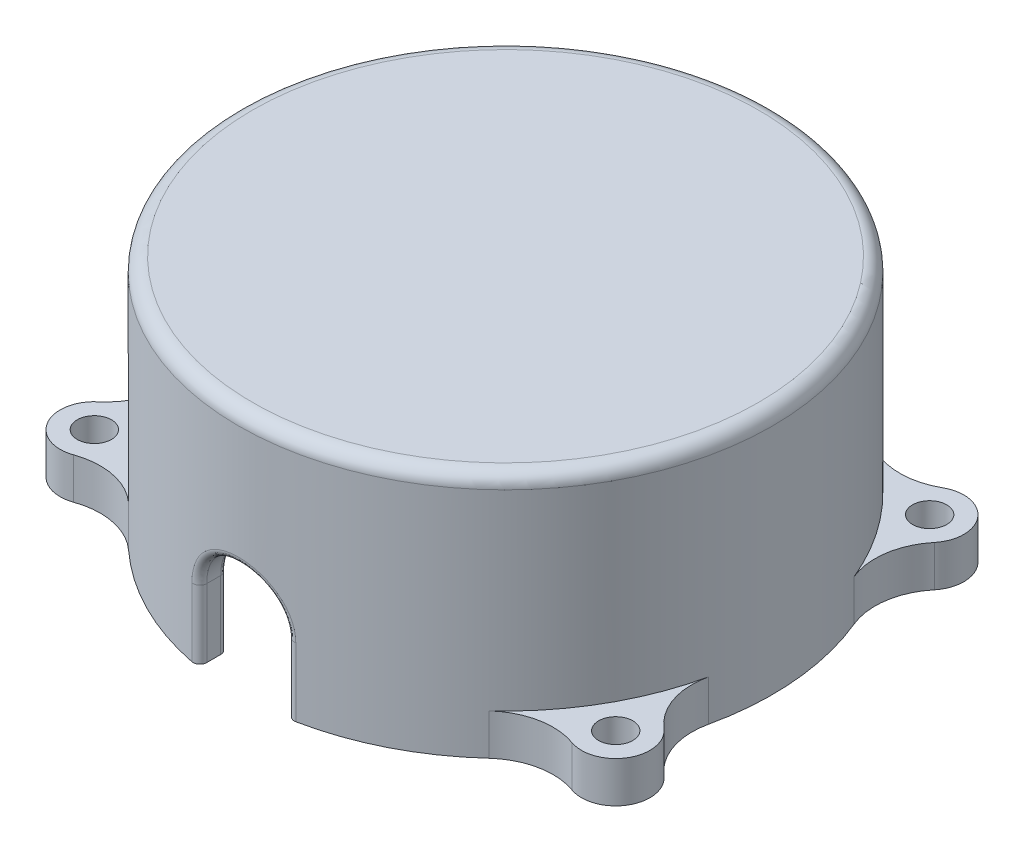
SolidWorks part; units mm, degrees
ref_plane "Спереди" through (0, 0, 0) normal (0, 0, 1) x (1, 0, 0)
ref_plane "Сверху" through (0, 0, 0) normal (0, 1, 0) x (1, 0, 0)
ref_plane "Справа" through (0, 0, 0) normal (1, 0, 0) x (0, 0, -1)
sketch "Эскиз1" plane through (0, 0, 0) normal (0, 0, 1) x (1, 0, 0)
  line L6 (0, 16) -> (0, 18)
  line L7 (0, 18) -> (19.5, 18)
  line L9 (19.5, 0) -> (17.5, 0)
  line L11 (17.5, 16) -> (0, 16)
  line L13 (17.5, 0) -> (17.5, 16)
  line L15 (19.5, 0) -> (19.5, 18)
  dimension "D3" = 16
  dimension "D4" = 2
  dimension "D5" = 2
  dimension "D6" = 17.5
revolve "Повернуть1" add sketch "Эскиз1" angle 360 about L6
sketch "Эскиз2" plane through (0, 0, 0) normal (0, -1, 0) x (1, 0, 0)
  line L0 (0, -22) -> (0, 0) construction
  line L1 (0, 0) -> (-22, 0) construction
  line L2 (16.853, -14.1413) -> (0, 0) construction
  line L3 (0, 0) -> (19.0526, 11) construction
  line L4 (15.246, -16.0564) -> (13.2076, -14.346)
  line L5 (18.4599, -12.2262) -> (16.4216, -10.5158)
  line L6 (-18.4599, -12.2262) -> (-16.4216, -10.5158)
  line L7 (-15.246, -16.0564) -> (-13.2076, -14.346)
  line L8 (17.8026, 13.1651) -> (15.4981, 11.8346)
  line L9 (20.3026, 8.8349) -> (17.9981, 7.5045)
  line L10 (-20.3026, 8.8349) -> (-17.9981, 7.5045)
  line L11 (-17.8026, 13.1651) -> (-15.4981, 11.8346)
  circle A1 centre (0, 0) radius 22 construction
  arc A2 (20.3026, 8.8349) -> (17.8026, 13.1651) centre (19.0526, 11) ccw
  arc A3 (15.246, -16.0564) -> (18.4599, -12.2262) centre (16.853, -14.1413) ccw
  circle A4 centre (16.853, -14.1413) radius 1.25
  circle A5 centre (19.0526, 11) radius 1.25
  circle A6 centre (-19.0526, 11) radius 1.25
  circle A7 centre (-16.853, -14.1413) radius 1.25
  arc A8 (-15.246, -16.0564) -> (-18.4599, -12.2262) centre (-16.853, -14.1413) cw
  arc A9 (-20.3026, 8.8349) -> (-17.8026, 13.1651) centre (-19.0526, 11) cw
  arc A10 (-16.4216, -10.5158) -> (-13.2076, -14.346) centre (0, 0) ccw
  circle A11 centre (0, 0) radius 19.5 construction
  arc A12 (-15.4981, 11.8346) -> (-17.9981, 7.5045) centre (0, 0) ccw
  arc A13 (17.9981, 7.5045) -> (15.4981, 11.8346) centre (0, 0) ccw
  arc A14 (13.2076, -14.346) -> (16.4216, -10.5158) centre (0, 0) ccw
  dimension "D1" = 44
  dimension "D2" = 2.5
  dimension "D3" = 5
  dimension "D4" = 50
  dimension "D5" = 120
extrude "Наплывы под шурупы" add sketch "Эскиз2" against normal blind 3
fillet "Скругление2" radius 3 1 edges at (17.5, 16, 0)
fillet "Скругление наплывов" radius 5 8 edges at (15.4981, 1.5, 11.8346) (17.9981, 1.5, 7.5045) (16.4216, 1.5, -10.5158) (13.2076, 1.5, -14.346) (-13.2076, 1.5, -14.346) (-16.4216, 1.5, -10.5158) (-17.9981, 1.5, 7.5045) (-15.4981, 1.5, 11.8346)
sketch "Эскиз4" plane through (0, 0, 0) normal (0, 0, 1) x (1, 0, 0)
  line L0 (-3.2, 5) -> (-3.2, 0)
  line L1 (-13.1693, 0) -> (13.1693, 0) construction
  line L2 (-3.2, 0) -> (3.2, 0)
  line L3 (3.2, 0) -> (3.2, 5)
  arc A0 (3.2, 5) -> (-3.2, 5) centre (0, 5) ccw
  dimension "D1" = 3.2
  dimension "D2" = 5
extrude "Паз под провода" cut sketch "Эскиз4" along normal up to next
fillet "Скругление4" radius 0.5 6 edges at (-0.3499, 8.1808, 19.4969) (3.2, 2.5, 19.2356) (-3.2, 2.5, 19.2356) (-3.2, 2.5, 17.2049) (3.2, 2.5, 17.2049) (0.345, 8.1813, 17.4966)
fillet "Скругление5" radius 1 1 edges at (19.5, 18, 0)
